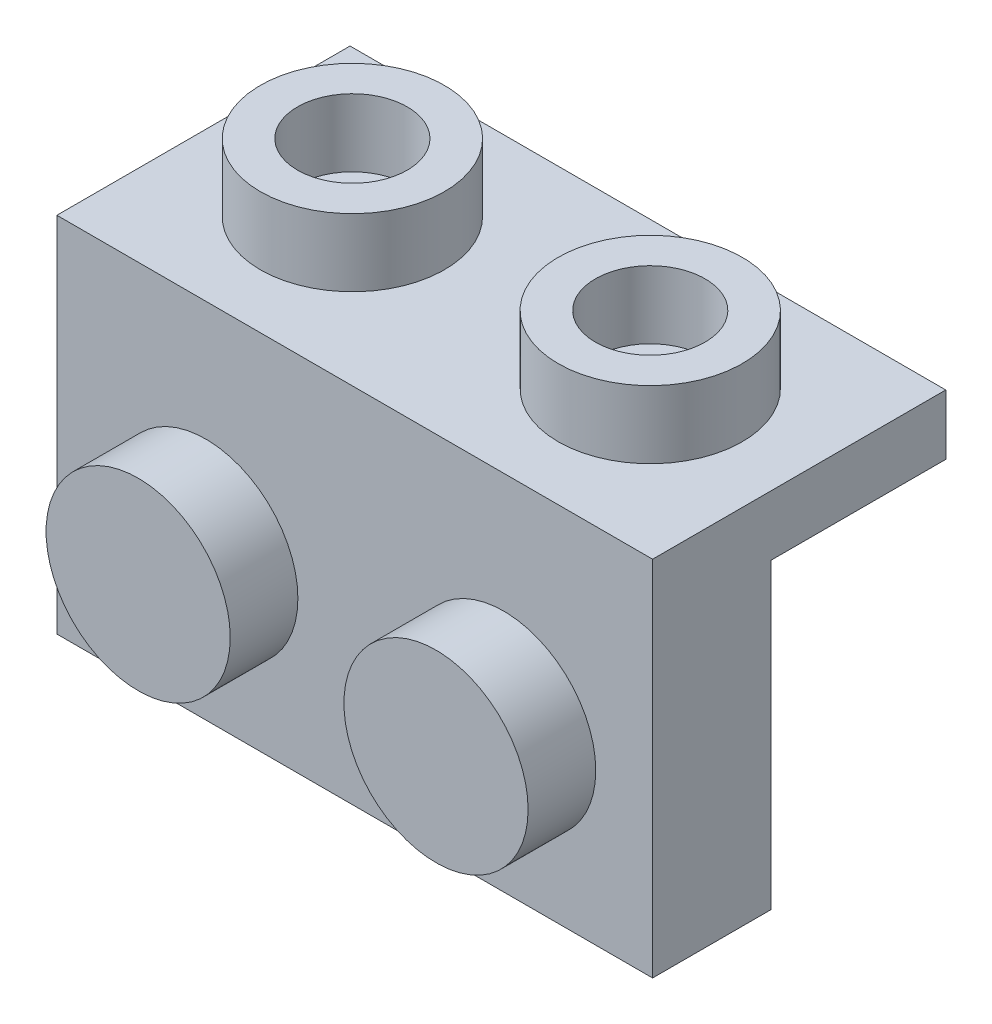
SolidWorks part; units mm, degrees
ref_plane "Front Plane" through (0, 0, 0) normal (0, 0, 1) x (1, 0, 0)
ref_plane "Top Plane" through (0, 0, 0) normal (0, 1, 0) x (1, 0, 0)
ref_plane "Right Plane" through (0, 0, 0) normal (1, 0, 0) x (0, 0, -1)
sketch "Sketch1" plane through (0, 0, 0) normal (1, 0, 0) x (0, 0, -1)
  line L0 (0, 0) -> (0, -9.65)
  line L1 (0, -9.65) -> (3.15, -9.65)
  line L2 (3.15, -9.65) -> (3.15, -1.6)
  line L3 (3.15, -1.6) -> (7.8, -1.6)
  line L4 (7.8, -1.6) -> (7.8, 0)
  line L5 (7.8, 0) -> (0, 0)
  dimension "D1" = 7.8
  dimension "D2" = 9.65
  dimension "D3" = 1.6
  dimension "D4" = 3.15
extrude "Boss-Extrude1" add sketch "Sketch1" against normal blind 15.85
sketch "Sketch2" plane through (0, 0, 0) normal (0, 1, 0) x (1, 0, 0)
  line L1 (-15.85, 7.8) -> (-15.85, 0) construction
  line L2 (0, 7.8) -> (0, 0) construction
  line L3 (-15.85, 0) -> (0, 0) construction
  circle A0 centre (-11.8875, 3.9) radius 2.45
  circle A1 centre (-11.8875, 3.9) radius 1.46
  circle A2 centre (-3.9625, 3.9) radius 2.45
  circle A3 centre (-3.9625, 3.9) radius 1.46
  dimension "D1" = 3.9625
  dimension "D2" = 3.9625
  dimension "D5" = 4.9
  dimension "D6" = 4.9
  dimension "D7" = 2.92
  dimension "D8" = 2.92
  dimension "D3" = 3.9
  dimension "D4" = 3.9
extrude "Boss-Extrude2" add sketch "Sketch2" along normal blind 1.8
sketch "Sketch3" plane through (0, 0, 0) normal (0, 0, 1) x (1, 0, 0)
  line L1 (-15.85, -9.65) -> (0, -9.65) construction
  line L4 (0, 0) -> (0, -9.65) construction
  line L6 (-15.85, 0) -> (-15.85, -9.65) construction
  circle A0 centre (-11.8875, -5.625) radius 2.45
  circle A1 centre (-3.9625, -5.625) radius 2.45
  dimension "D3" = 3.9625
  dimension "D4" = 3.9625
  dimension "D5" = 4.9
  dimension "D6" = 4.9
  dimension "D1" = 4.025
  dimension "D2" = 4.025
extrude "Boss-Extrude3" add sketch "Sketch3" along normal blind 1.8
shell "Shell1" thickness 1.5 removed face at (-7.925, -5.625, -3.15)
